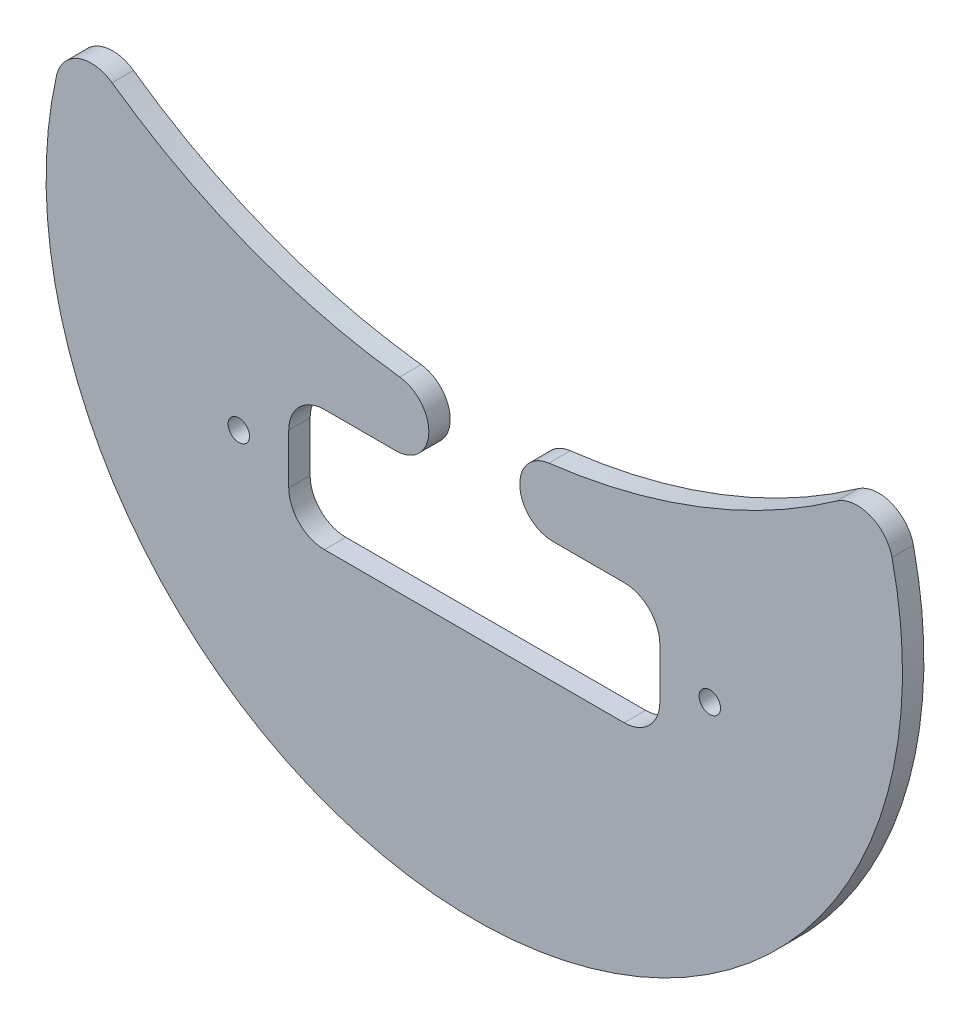
SolidWorks part; units mm, degrees
ref_plane "Front Plane" through (0, 0, 0) normal (0, 0, 1) x (1, 0, 0)
ref_plane "Top Plane" through (0, 0, 0) normal (0, 1, 0) x (1, 0, 0)
ref_plane "Right Plane" through (0, 0, 0) normal (1, 0, 0) x (0, 0, -1)
sketch "Sketch1" plane through (0, 0, 0) normal (0, 0, 1) x (1, 0, 0)
  line L1 (0.1514, 32.35) -> (0.1514, 52.6395) construction
  line L2 (-25.8486, 6.75) -> (26.1514, 6.75)
  line L3 (-25.8486, 6.75) -> (-25.8486, 23.75)
  line L4 (-25.8486, 23.75) -> (-10.8486, 23.75)
  line L5 (26.1514, 6.75) -> (26.1514, 23.75)
  line L6 (11.1514, 23.75) -> (26.1514, 23.75)
  arc A0 (-56.2301, 52.8712) -> (56.533, 52.8712) centre (0.1514, 32.35) ccw
  arc A1 (-56.2301, 52.8712) -> (-10.2972, 32.9745) centre (0.1514, 120.0641) ccw
  arc A2 (-10.2972, 32.9745) -> (-10.8486, 23.75) centre (-10.8486, 28.3788) cw
  arc A3 (10.6, 32.9745) -> (11.1514, 23.75) centre (11.1514, 28.3788) ccw
  arc A4 (10.6, 32.9745) -> (56.533, 52.8712) centre (0.1514, 120.0641) ccw
  circle A5 centre (-32.8486, 15.25) radius 1.5
  circle A6 centre (33.1514, 15.25) radius 1.5
  point P3 (0.1514, 32.35)
  point P8 (0.1514, -27.65)
  point P28 (0, 0)
  dimension "D2" = 60
  dimension "D3" = 140
  dimension "D5" = 3
  dimension "D4" = 15
extrude "Boss-Extrude1" add sketch "Sketch1" along normal blind 3
fillet "Fillet4" radius 5 6 edges at (-25.8486, 23.75, 1.5) (-25.8486, 6.75, 1.5) (26.1514, 6.75, 1.5) (26.1514, 23.75, 1.5) (-56.2301, 52.8712, 1.5) (56.533, 52.8712, 1.5)
